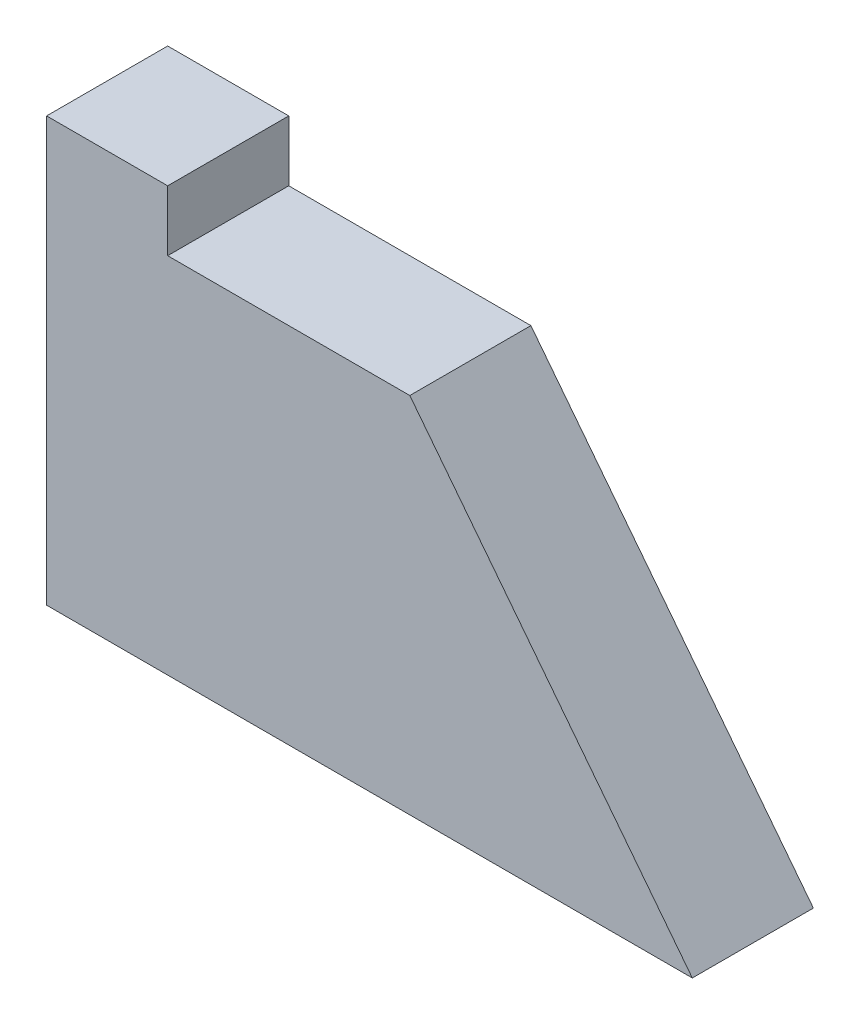
SolidWorks part; units mm, degrees
ref_plane "Спереди" through (0, 0, 0) normal (0, 0, 1) x (1, 0, 0)
ref_plane "Сверху" through (0, 0, 0) normal (0, 1, 0) x (1, 0, 0)
ref_plane "Справа" through (0, 0, 0) normal (1, 0, 0) x (0, 0, -1)
sketch "Эскиз1" plane through (0, 0, 0) normal (0, 0, 1) x (1, 0, 0)
  line L0 (0, 9) -> (0, 0)
  line L1 (0, 0) -> (16, 0)
  line L2 (16, 0) -> (9, 9)
  line L3 (9, 9) -> (0, 9)
  dimension "D1" = 9
  dimension "D2" = 9
  dimension "D3" = 16
extrude "Бобышка-Вытянуть1" add sketch "Эскиз1" along normal blind 3
sketch "Эскиз2" plane through (0, 9, 0) normal (0, 1, 0) x (1, 0, 0)
  line L0 (0, -3) -> (0, 0) construction
  line L1 (0, 0) -> (3, 0)
  line L2 (0, 0) -> (0, -3)
  line L3 (0, -3) -> (3, -3)
  line L4 (3, 0) -> (3, -3)
  line L7 (9, -3) -> (0, -3) construction
  line L8 (9, 0) -> (0, 0) construction
  dimension "D1" = 3
extrude "Бобышка-Вытянуть2" add sketch "Эскиз2" along normal blind 1.5
sketch "Эскиз3" plane through (0, 0, 0) normal (0, -1, 0) x (1, 0, 0)
  line L0 (0, 3) -> (16, 3) construction
  line L1 (0, 0) -> (5.5, 0)
  line L2 (0, 0) -> (0, 3)
  line L3 (0, 3) -> (5.5, 3)
  line L4 (5.5, 0) -> (5.5, 3)
  dimension "D1" = 5.5
extrude "Бобышка-Вытянуть3" [suppressed] add sketch "Эскиз3" along normal blind 1.5
